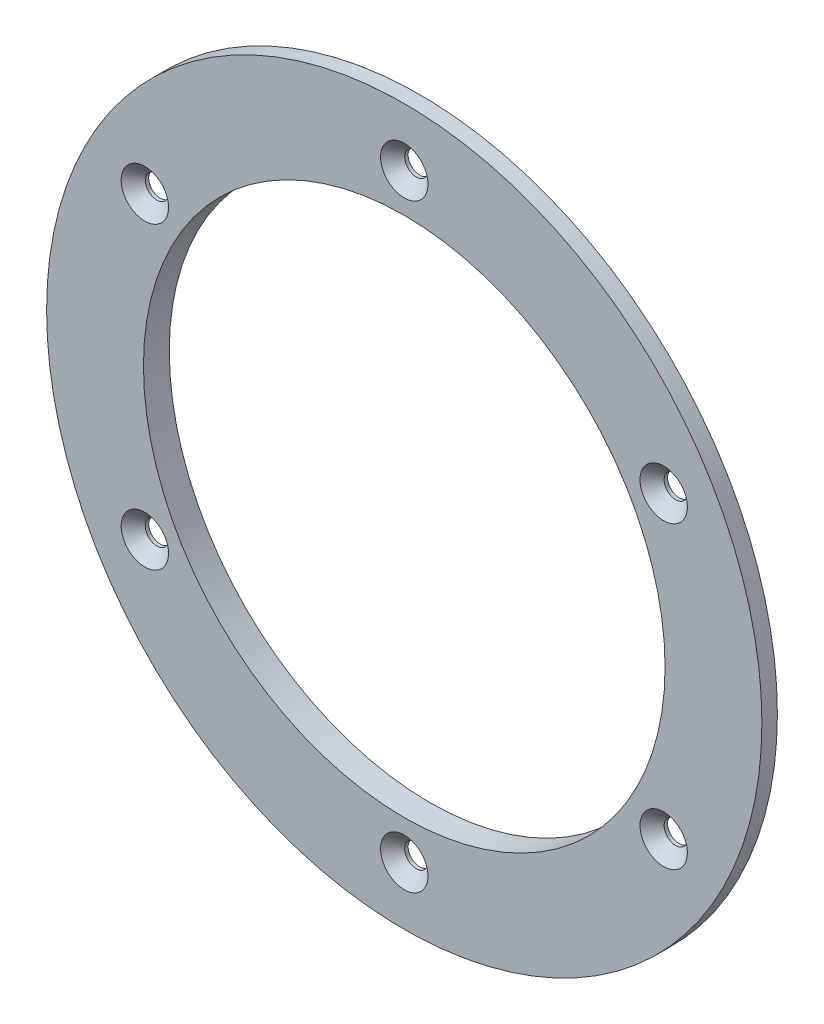
SolidWorks part; units mm, degrees
material "7079 Alloy"
ref_plane "Front Plane" through (0, 0, 0) normal (0, 0, 1) x (1, 0, 0)
ref_plane "Top Plane" through (0, 0, 0) normal (0, 1, 0) x (1, 0, 0)
ref_plane "Right Plane" through (0, 0, 0) normal (1, 0, 0) x (0, 0, -1)
sketch "Sketch1" plane through (0, 0, 0) normal (0, 0, 1) x (1, 0, 0)
  circle A0 centre (0, 0) radius 50.5
  circle A1 centre (0, 0) radius 69.25
  dimension "D1" = 101
  dimension "D2" = 138.5
extrude "Extrude1" add sketch "Sketch1" along normal blind 3
sketch "Sketch2" plane through (0, 0, 3) normal (0, 0, 1) x (1, 0, 0)
  line L0 (0, 0) -> (0, 58) construction
  circle A0 centre (0, 58) radius 2
  dimension "D1" = 4
  dimension "D2" = 58
extrude "Cut-Extrude1" cut sketch "Sketch2" against normal blind 10
hole_wizard "CSK for M4 Hex Socket Countersunk Head Screw1" positions "3DSketch1" profile "Sketch3" countersink size "M4" standard "DIN" end condition through all
sketch3d "3DSketch1"
  line L0 (0, 58, 0) -> (0, 58, 3) construction
  point P0 (0, 58, 3)
sketch "Sketch3" plane through (0, 58, 3) normal (1, 0, 0) x (0, -1, 0)
  line L0 (0, 0) -> (0, 3)
  line L1 (0, 3) -> (2.25, 3)
  line L2 (2.25, 3) -> (2.25, 2.34)
  line L3 (2.25, 2.34) -> (4.59, 0)
  line L5 (4.59, 0) -> (0, 0)
  line L6 (-2.25, 2.34) -> (-4.59, 0) construction
  line L11 (0, -6.35) -> (0, 107.95) construction
  dimension "Thru Hole Dia." = 4.5
  dimension "Thru Hole Depth" = 3
  dimension "Near C'Sink Dia." = 9.18
  dimension "Near C'Sink Angle" = 90
ref_axis "Axis1" through (0, 0, 3) along (0, 0, -1)
pattern_circular "CirPattern1" count 6 over 360 about axis through (0, 0, 3) along (0, 0, -1) of "CSK for M4 Hex Socket Countersunk Head Screw1"
sketch "Sketch4" plane through (0, 0, 0) normal (0, 0, -1) x (-1, 0, 0)
  circle A0 centre (0, 0) radius 52.5
  circle A1 centre (0, 0) radius 50.5 construction
  circle A2 centre (0, 0) radius 50.5
  dimension "D1" = 2
extrude "Boss-Extrude1" add sketch "Sketch4" along normal blind 2
